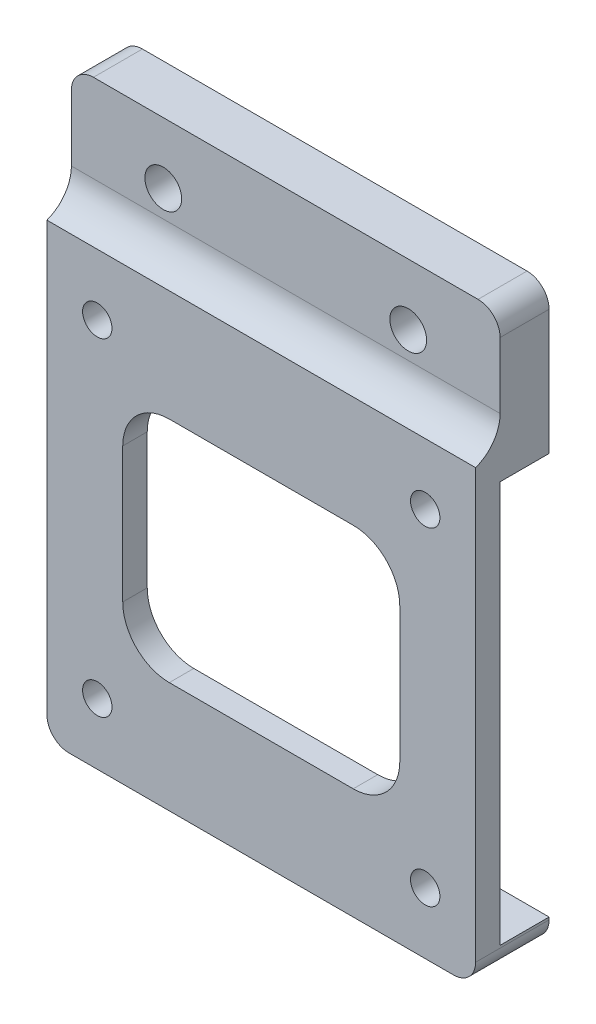
SolidWorks part; units mm, degrees
ref_plane "Front Plane" through (0, 0, 0) normal (0, 0, 1) x (1, 0, 0)
ref_plane "Top Plane" through (0, 0, 0) normal (0, 1, 0) x (1, 0, 0)
ref_plane "Right Plane" through (0, 0, 0) normal (1, 0, 0) x (0, 0, -1)
sketch "Sketch1" plane through (0, 0, 0) normal (0, 0, 1) x (1, 0, 0)
  line L0 (0, 0) -> (25.4, 0) construction
  line L1 (-9.525, 6.35) -> (34.925, 6.35)
  line L2 (-9.525, 6.35) -> (-9.525, -53.05)
  line L3 (-9.525, -53.05) -> (34.925, -53.05)
  line L4 (34.925, 6.35) -> (34.925, -53.05)
  line L5 (-4.3, -12.7) -> (29.7, -12.7) construction
  circle A0 centre (0, 0) radius 1.905
  circle A1 centre (25.4, 0) radius 1.905
  circle A2 centre (-4.3, -12.7) radius 1.524
  circle A3 centre (29.7, -12.7) radius 1.524
  circle A4 centre (29.7, -46.7) radius 1.524
  circle A5 centre (-4.3, -46.7) radius 1.524
  point P5 (12.7, 0)
  point P10 (12.7, 6.35)
  point P19 (12.7, -12.7)
  point P20 (0, 0)
  dimension "D2" = 3.81
  dimension "D9" = 3.048
  dimension "D1" = 25.4
  dimension "D3" = 34
  dimension "D4" = 34
  dimension "D5" = 44.45
  dimension "D6" = 6.35
  dimension "D7" = 12.7
  dimension "D8" = 6.35
extrude "Boss-Extrude1" add sketch "Sketch1" along normal blind 5.08
sketch "Sketch2" plane through (0, 0, 5.08) normal (0, 0, 1) x (1, 0, 0)
  line L0 (34.925, -53.05) -> (34.925, 6.35) construction
  line L1 (-9.525, -53.05) -> (34.925, -53.05)
  line L2 (-9.525, -53.05) -> (-9.525, -6.35)
  line L3 (-9.525, -6.35) -> (34.925, -6.35)
  line L4 (34.925, -53.05) -> (34.925, -6.35)
  circle A0 centre (-4.3, -12.7) radius 1.524 construction
  circle A19 centre (-4.3, -12.7) radius 1.524
  circle A20 centre (-4.3, -46.7) radius 1.524
  circle A21 centre (29.7, -12.7) radius 1.524
  circle A22 centre (29.7, -46.7) radius 1.524
  circle A23 centre (29.7, -12.7) radius 1.524 construction
  circle A24 centre (-4.3, -46.7) radius 1.524 construction
  circle A25 centre (29.7, -46.7) radius 1.524 construction
  dimension "D1" = 6.35
extrude "Boss-Extrude2" add sketch "Sketch2" along normal blind 2.54
sketch "Sketch3" plane through (0, 0, 0) normal (0, 0, -1) x (-1, 0, 0)
  line L0 (-34.925, -53.05) -> (-34.925, 6.35) construction
  line L1 (-34.925, -8.89) -> (9.525, -8.89)
  line L2 (-34.925, -8.89) -> (-34.925, -50.51)
  line L3 (-34.925, -50.51) -> (9.525, -50.51)
  line L4 (9.525, -8.89) -> (9.525, -50.51)
  line L5 (9.525, 6.35) -> (9.525, -53.05) construction
  circle A0 centre (-29.7, -12.7) radius 1.524 construction
  circle A1 centre (-29.7, -46.7) radius 1.524 construction
  dimension "D1" = 3.81
  dimension "D2" = 3.81
extrude "Cut-Extrude1" cut sketch "Sketch3" against normal blind 5.08 contours L1 L4 L3 L2
fillet "Fillet2" radius 2.286 4 edges at (34.925, -53.05, 3.81) (-9.525, -53.05, 3.81) (-9.525, 6.35, 2.54) (34.925, 6.35, 2.54)
sketch "Sketch4" plane through (0, 0, 7.62) normal (0, 0, 1) x (1, 0, 0)
  line L0 (29.7, -12.7) -> (-4.3, -12.7) construction
  line L1 (-1.662, -17.8681) -> (27.062, -17.8681)
  line L2 (-1.662, -17.8681) -> (-1.662, -41.5319)
  line L3 (-1.662, -41.5319) -> (27.062, -41.5319)
  line L4 (27.062, -17.8681) -> (27.062, -41.5319)
  line L5 (-4.3, -12.7) -> (-4.3, -46.7) construction
  point P8 (-4.3, -29.7)
  point P11 (12.7, -12.7)
  point P12 (12.7, -17.8681)
  point P13 (-1.662, -29.7)
  point P14 (0, 0)
  point P15 (0, 0)
extrude "Cut-Extrude2" cut sketch "Sketch4" against normal through all contours L1 L4 L3 L2
fillet "Fillet3" radius 4.826 4 edges at (27.062, -41.5319, 6.35) (-1.662, -41.5319, 6.35) (27.062, -17.8681, 6.35) (-1.662, -17.8681, 6.35)
fillet "Fillet4" radius 3.81 1 edges at (12.7, -6.35, 5.08)
